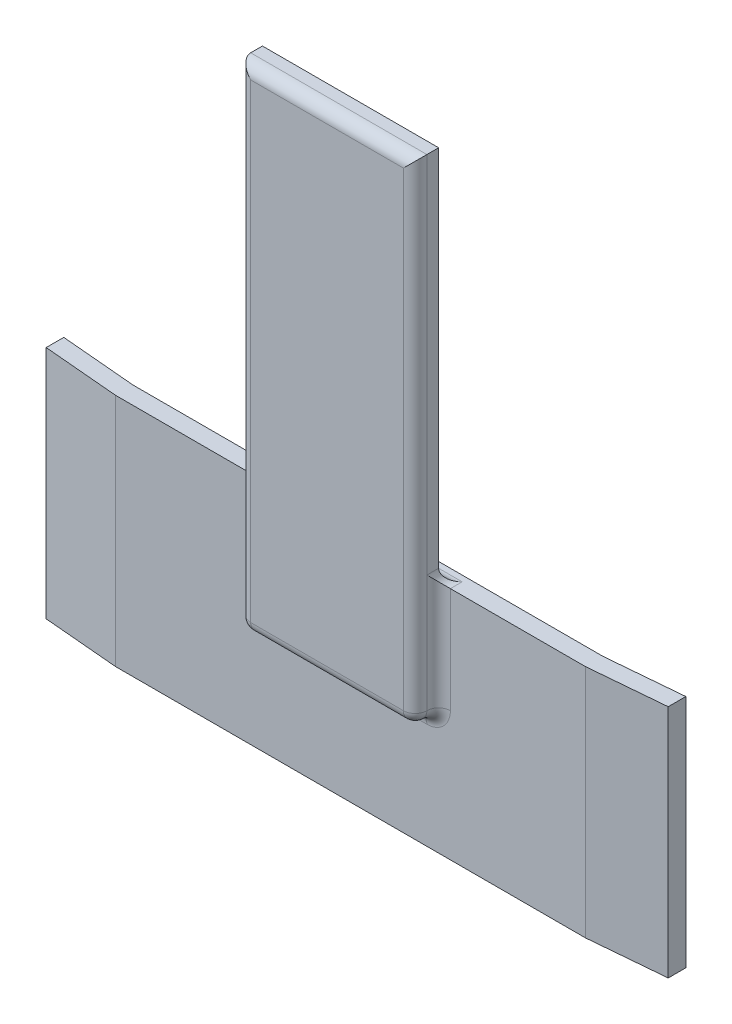
SolidWorks part; units mm, degrees
material "ABS"
ref_plane "Front Plane" through (0, 0, 0) normal (0, 0, 1) x (1, 0, 0)
ref_plane "Top Plane" through (0, 0, 0) normal (0, 1, 0) x (1, 0, 0)
ref_plane "Right Plane" through (0, 0, 0) normal (1, 0, 0) x (0, 0, -1)
sketch "Sketch1" plane through (0, 0, 0) normal (0, 0, 1) x (1, 0, 0)
  line L1 (-50.8, -25.4) -> (50.8, -25.4)
  line L2 (-50.8, -25.4) -> (-50.8, 25.4)
  line L3 (-50.8, 25.4) -> (50.8, 25.4)
  line L4 (50.8, -25.4) -> (50.8, 25.4)
  line L5 (-50.8, -25.4) -> (50.8, 25.4) construction
  line L6 (-50.8, 25.4) -> (50.8, -25.4) construction
  point P0 (0, 0)
  dimension "D1" = 101.6
  dimension "D2" = 50.8
extrude "Boss-Extrude2" add sketch "Sketch1" along normal blind 3.81 contours L3 L4 L1 L2
ref_plane "Plane1" through (0.7167, 0, 8.1917) normal (-0.0872, 0, -0.9962) x (0, 1, 0)
sketch "Sketch2" plane through (0.7167, 0, 8.1917) normal (-0.0872, 0, -0.9962) x (0, 1, 0)
  line L0 (25.4, 50.2746) -> (-25.4, 50.2746)
  line L1 (-25.4, 50.2746) -> (-25.4, 66.7846)
  line L2 (-25.4, 66.7846) -> (25.4, 66.7846)
  line L3 (25.4, 66.7846) -> (25.4, 50.2746)
  dimension "D1" = 16.51
extrude "Boss-Extrude4" add sketch "Sketch2" along direction (0, 0, -1) on the side of the normal blind 3.81 contours L3 L0 L1 L2
ref_plane "Plane2" through (0, 0, 0) normal (-1, 0, 0) x (0, 0, 1)
mirror "Mirror1" about plane through (0, 0, 0) normal (-1, 0, 0) of "Boss-Extrude4"
sketch "Sketch4" plane through (0, 0, 3.81) normal (0, 0, 1) x (1, 0, 0)
  line L0 (-19.05, 0) -> (19.05, 0)
  line L5 (19.05, 0) -> (19.05, 106.68)
  line L6 (19.05, 106.68) -> (-19.05, 106.68)
  line L7 (-19.05, 106.68) -> (-19.05, 0)
  point P4 (0, 0)
  dimension "D1" = 106.68
  dimension "D2" = 38.1
extrude "Boss-Extrude5" add sketch "Sketch4" along normal blind 5.08
fillet "Fillet1" radius 2.54 7 edges at (-19.05, 12.7, 3.81) (19.05, 12.7, 3.81) (0, 0, 3.81) (19.05, 53.34, 8.89) (0, 0, 8.89) (-19.05, 53.34, 8.89) (0, 106.68, 8.89)
fillet "Fillet18" radius 2.54 1 edges at (0, 25.4, 3.81)
fillet "Fillet19" radius 2.54 1 edges at (19.05, 25.4, 3.81)
fillet "Fillet20" radius 2.54 1 edges at (-19.05, 25.4, 3.81)
